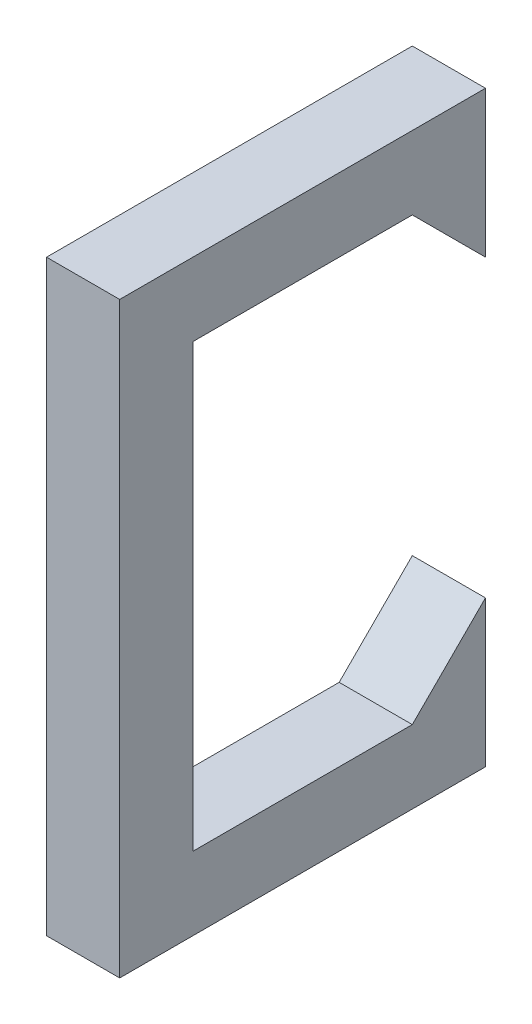
SolidWorks part; units mm, degrees
ref_plane "Front Plane" through (0, 0, 0) normal (0, 0, 1) x (1, 0, 0)
ref_plane "Top Plane" through (0, 0, 0) normal (0, 1, 0) x (1, 0, 0)
ref_plane "Right Plane" through (0, 0, 0) normal (1, 0, 0) x (0, 0, -1)
sketch "Sketch1" plane through (0, 0, 0) normal (0, 0, 1) x (1, 0, 0)
  line L1 (0, 9.05) -> (1.5, 9.05)
  line L2 (0, 9.05) -> (0, 0)
  line L3 (0, 0) -> (1.5, 0)
  line L4 (1.5, 9.05) -> (1.5, 0)
  line L5 (0, 9.05) -> (1.5, 9.05)
  line L6 (0, 9.05) -> (0, 10.55)
  line L7 (0, 10.55) -> (1.5, 10.55)
  line L8 (1.5, 9.05) -> (1.5, 10.55)
  line L9 (0, 0) -> (1.5, 0)
  line L10 (0, 0) -> (0, -1.5)
  line L11 (0, -1.5) -> (1.5, -1.5)
  line L12 (1.5, 0) -> (1.5, -1.5)
  dimension "D1" = 1.5
  dimension "D2" = 9.05
  dimension "D3" = 1.5
  dimension "D4" = 1.5
extrude "Boss-Extrude1" add sketch "Sketch1" along normal blind 1.5 contours L4 L1 L2 L3 | L1 L8 L7 L6 | L12 L3 L10 L11 region at (0.75, 9.8, 0) region at (0.75, 4.525, 0) region at (0.75, -0.75, 0)
extrude "Boss-Extrude2" add sketch "Sketch1<3>" against normal blind 6 contours L1 L8 L7 L6 | L12 L3 L10 L11 region at (0.75, 9.8, 0) region at (0.75, -0.75, 0)
sketch "Sketch1<3>" plane through (0, 0, 0) normal (0, 0, 1) x (1, 0, 0) same geometry as "Sketch1"
sketch "Sketch2" plane through (1.5, 0, 0) normal (1, 0, 0) x (0, 0, -1)
  line L0 (4.5, 9.05) -> (6, 7.55)
  line L1 (6, 9.05) -> (4.5, 9.05)
  line L2 (6, 9.05) -> (6, 7.55)
  line L5 (6, 0) -> (4.5, 0)
  line L6 (6, 0) -> (6, 1.5)
  line L9 (6, 1.5) -> (4.5, 0)
  dimension "D1" = 1.5
  dimension "D3" = 1.5
  dimension "D2" = 45
  dimension "D4" = 45
extrude "Boss-Extrude3" add sketch "Sketch2" against normal up to surface (1.5 mm away) up to face at (0, 4.525, -2.625)
ref_plane "Vertical Inside Plane" through (0, 0, 0) normal (0, 0, -1) x (-1, 0, 0)
ref_plane "Bottom Plane" through (0, 0, 0) normal (0, 1, 0) x (1, 0, 0)
ref_plane "Side Plane" through (0, 0, 0) normal (-1, 0, 0) x (0, 0, 1)
equation "\"acryllic\"= 2.85mm"
equation "\"wall\"= 1.5mm"
equation "\"laserOD\"= 6.34mm + 2 * \"wall\""
equation "\"tankL\"= 7.5cm"
equation "\"tankW\"= 5cm"
equation "\"edgeClr\"= \"tankW\" / \"edgeClr_a\""
equation "\"edgeClr_a\"= 2'edgeClr_a determines how big turret edge clearance is"
equation "\"acryllicSkirt\"= .5mm"
equation "\"D1@Sketch1\"=\"wall\""
equation "\"D2@Sketch1\"=\"acryllic\"*3+2*\"clr\""
equation "\"D3@Sketch1\"=\"wall\""
equation "\"D4@Sketch1\"=\"wall\""
equation "\"D1@Boss-Extrude1\"=\"wall\""
equation "\"D1@Boss-Extrude2\"=\"wall\"*4"
equation "\"D1@Sketch2\"=\"wall\""
equation "\"D3@Sketch2\"=\"wall\""
equation "\"clr\"= .25mm"
